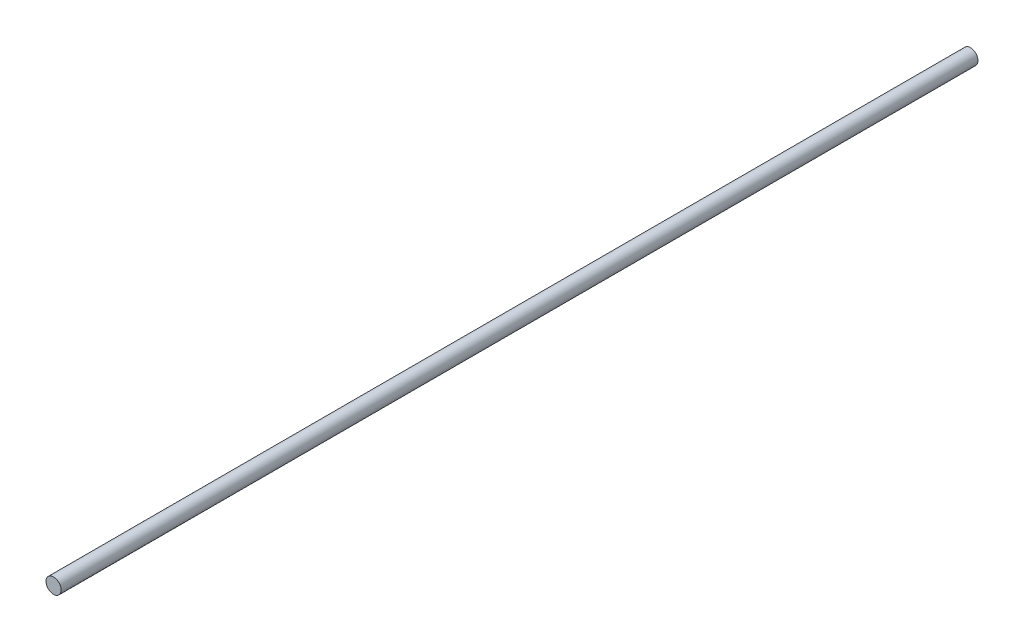
SolidWorks part; units mm, degrees
ref_plane "Alzado" through (0, 0, 0) normal (0, 0, 1) x (1, 0, 0)
ref_plane "Planta" through (0, 0, 0) normal (0, 1, 0) x (1, 0, 0)
ref_plane "Vista lateral" through (0, 0, 0) normal (1, 0, 0) x (0, 0, -1)
sketch "Croquis1" plane through (0, 0, 0) normal (0, 0, 1) x (1, 0, 0)
  circle A0 centre (0, 0) radius 5
  dimension "D1" = 10
extrude "Saliente-Extruir1" add sketch "Croquis1" along normal blind 605.8
